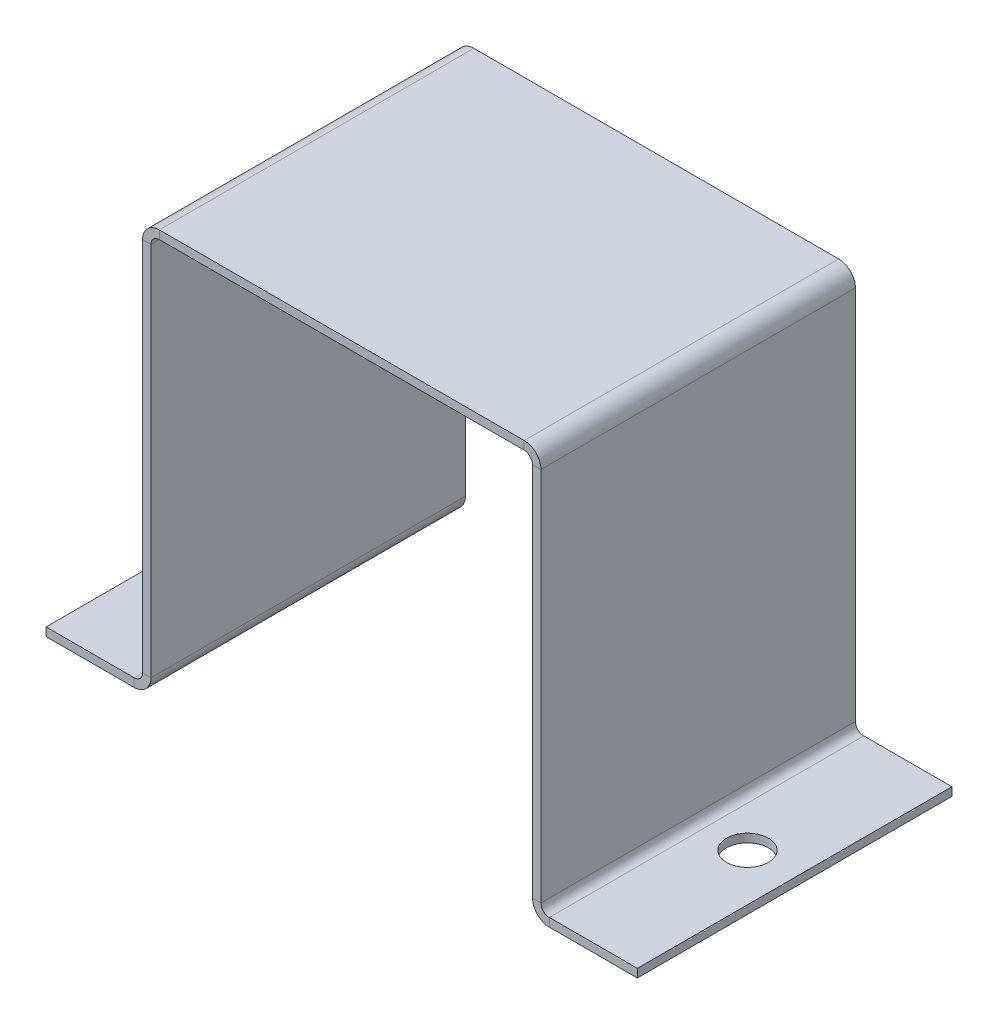
SolidWorks part; units mm, degrees
note: The reader was unsure of these and kept them because the rebuilt part matched: flange length of "Edge-Flange1", "Edge-Flange2".
material "AISI 1020 Steel, Cold Rolled"
ref_plane "Front Plane" through (0, 0, 0) normal (0, 0, 1) x (1, 0, 0)
ref_plane "Top Plane" through (0, 0, 0) normal (0, 1, 0) x (1, 0, 0)
ref_plane "Right Plane" through (0, 0, 0) normal (1, 0, 0) x (0, 0, -1)
sketch "Sketch1" plane through (0, 0, 0) normal (0, 1, 0) x (1, 0, 0)
  line L1 (-19, -15) -> (19, -15)
  line L2 (-19, -15) -> (-19, 15)
  line L3 (-19, 15) -> (19, 15)
  line L4 (19, -15) -> (19, 15)
  line L5 (-19, -15) -> (19, 15) construction
  line L6 (-19, 15) -> (19, -15) construction
  point P0 (0, 0)
  dimension "D1" = 38
  dimension "D2" = 30
sheet metal parameters "Sheet-Metal1" thickness 0.8 parameters "D1"=0.8
base flange "Base-Flange1" sketch "Sketch1" thickness 0.8 reverse thickness direction no parameters "D1"=0.8
edge flange "Edge-Flange1" sketch "Sketch7" flange profiles "Sketch7", "Sketch8" flange angle 90 flange length 39 flange position material inside bend radius 0.8 thickness 0.8 parameters "D6"=10, "D8"=0.04
sketch "Sketch7" plane through (-19, -0.8, 0) normal (1, 0, 0) x (0, 0, 1)
  line L1 (15, 0) -> (-15, 0) construction
  line L2 (-15, 0) -> (-15, 38.2)
  line L3 (-15, 38.2) -> (15, 38.2)
  line L4 (15, 38.2) -> (15, 0)
  line L5 (15, 0) -> (-15, 0)
sketch "Sketch8" plane through (19, -0.8, 0) normal (-1, 0, 0) x (0, 0, -1)
  line L0 (15, 0) -> (-15, 0) construction
  line L1 (15, 0) -> (-15, 0)
  line L2 (15, 0) -> (15, 38.2)
  line L3 (15, 38.2) -> (-15, 38.2)
  line L4 (-15, 38.2) -> (-15, 0)
bend "EdgeBend1" bend radius 0.8 bend angle 90 parameters "D5"=1
bend "EdgeBend2" bend radius 0.8 bend angle 90 parameters "D5"=2
edge flange "Edge-Flange2" sketch "Sketch13" flange profiles "Sketch13", "Sketch14" flange angle 90 flange length 10 flange position material inside bend radius 0.8 thickness 0.8 parameters "D6"=10, "D8"=0.04
sketch "Sketch13" plane through (-19, -39, 0) normal (0, -1, 0) x (0, 0, 1)
  line L0 (15, 0) -> (-15, 0) construction
  line L1 (15, 0) -> (-15, 0)
  line L2 (-15, 0) -> (-15, 9.2)
  line L3 (-15, 9.2) -> (15, 9.2)
  line L4 (15, 9.2) -> (15, 0)
sketch "Sketch14" plane through (19, -39, 0) normal (0, -1, 0) x (0, 0, -1)
  line L0 (15, 0) -> (-15, 0) construction
  line L1 (15, 0) -> (-15, 0)
  line L2 (-15, 0) -> (-15, 9.2)
  line L3 (-15, 9.2) -> (15, 9.2)
  line L4 (15, 9.2) -> (15, 0)
bend "EdgeBend3" bend radius 0.8 bend angle 90 parameters "D5"=3
bend "EdgeBend4" bend radius 0.8 bend angle 90 parameters "D5"=4
sketch "Sketch15" plane through (0, -38.2, 0) normal (0, 1, 0) x (1, 0, 0)
  line L0 (-28.2, -15) -> (-28.2, 15) construction
  line L1 (28.2, 15) -> (28.2, -15) construction
  circle A0 centre (-23.7, 0) radius 2
  circle A1 centre (23.7, 0) radius 2
  dimension "D1" = 4.5
  dimension "D2" = 4.5
extrude "Cut-Extrude1" cut sketch "Sketch15" against normal blind 10 normal cut yes
flat pattern "Flat-Pattern1" [suppressed]
sketch "Bend-Lines1" plane through (0, 0, 0) normal (0, 1, 0) x (-1, 0, 0)
bend of the flat pattern "Flatten-<EdgeBend1>1"
bend of the flat pattern "Flatten-<EdgeBend2>1"
bend of the flat pattern "Flatten-<EdgeBend3>1"
bend of the flat pattern "Flatten-<EdgeBend4>1"
